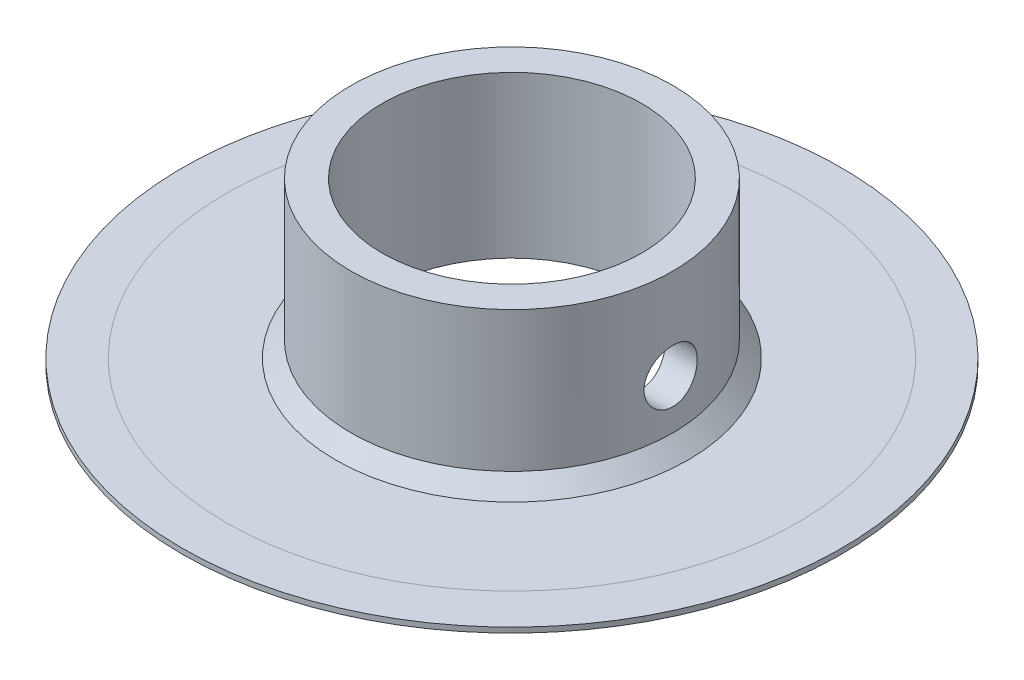
SolidWorks part; units mm, degrees
material "6063-T5"
ref_plane "Front Plane" through (0, 0, 0) normal (0, 0, 1) x (1, 0, 0)
ref_plane "Top Plane" through (0, 0, 0) normal (0, 1, 0) x (1, 0, 0)
ref_plane "Right Plane" through (0, 0, 0) normal (1, 0, 0) x (0, 0, -1)
sketch "Sketch1" plane through (0, 0, 0) normal (0, 1, 0) x (1, 0, 0)
  circle A0 centre (0, 0) radius 12.7
  dimension "D1" = 25.4
extrude "Boss-Extrude1" add sketch "Sketch1" along normal blind 0.2
sketch "Sketch2" plane through (0, 0.2, 0) normal (0, 1, 0) x (1, 0, 0)
  circle A0 centre (0, 0) radius 7
  dimension "D1" = 14
extrude "Boss-Extrude2" add sketch "Sketch2" along normal blind 0.8
sketch "Sketch3" plane through (0, 1, 0) normal (0, 1, 0) x (1, 0, 0)
  circle A0 centre (0, 0) radius 6.2
  dimension "D1" = 12.4
extrude "Boss-Extrude3" add sketch "Sketch3" along normal blind 5.2
chamfer "Chamfer1" distance 1 angle 45 1 edges at (0, 1, 7)
sketch "Sketch5" plane through (0, 6.2, 0) normal (0, 1, 0) x (1, 0, 0)
  circle A0 centre (0, 0) radius 5
  dimension "D1" = 10
extrude "Cut-Extrude1" cut sketch "Sketch5" against normal through all
sketch "Sketch8" plane through (0, 6.2, 0) normal (0, 1, 0) x (1, 0, 0)
  circle A0 centre (0, 0) radius 6.2 construction
  point P0 (6.2, 0)
hole_wizard "M2.5 Tapped Hole1" positions "3DSketch2" profile "Sketch10" tap size "M2.5" standard "ISO"
sketch3d "3DSketch2"
  point P0 (6.2, 2.7, 0)
  dimension "D1" = 3.5
sketch "Sketch10" plane through (6.2, 2.7, 0) normal (0, 1, 0) x (0, 0, -1)
  line L0 (0, 0) -> (0, 6.8149)
  line L1 (0, 6.8149) -> (1.025, 6.199)
  line L2 (1.025, 6.199) -> (1.025, 0)
  line L5 (1.025, 0) -> (0, 0)
  line L10 (0, 6.8149) -> (-1.025, 6.199) construction
  line L11 (0, -6.35) -> (0, 107.95) construction
  dimension "Tap Drill Dia." = 2.05
  dimension "Tap Drill Depth" = 6.199
  dimension "Drill Angle" = 118
cosmetic thread "Hole Thread1" parameters "D1"=3.3805, "D2"=2.5
sketch "Sketch11" plane through (0, 0.2, 0) normal (0, 1, 0) x (1, 0, 0)
  circle A0 centre (0, 0) radius 11
  dimension "D1" = 22
split line "Split Line1"
